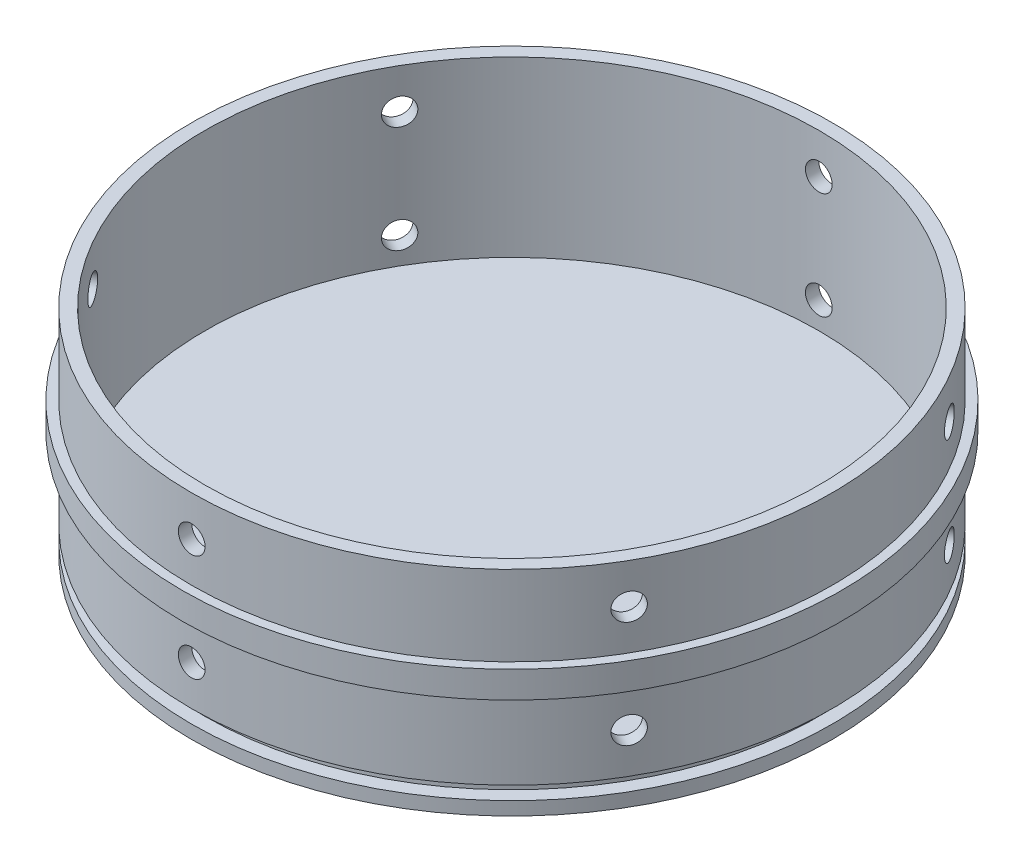
SolidWorks part; units mm, degrees
material "2024-T4"
ref_plane "Front Plane" through (0, 0, 0) normal (0, 0, 1) x (1, 0, 0)
ref_plane "Top Plane" through (0, 0, 0) normal (0, 1, 0) x (1, 0, 0)
ref_plane "Right Plane" through (0, 0, 0) normal (1, 0, 0) x (0, 0, -1)
sketch "Sketch1" plane through (0, 0, 0) normal (0, 1, 0) x (1, 0, 0)
  circle A0 centre (0, 0) radius 78.359
  circle A2 centre (0, 0) radius 76.2
  circle A3 centre (0, 0) radius 73.025
  dimension "D1" = 156.718
  dimension "D2" = 152.4
  dimension "D3" = 3.175
extrude "Boss-Extrude1" add sketch "Sketch1" along normal blind 6.35 contours A0 A2 region at (-78.1374, 0, 0)
extrude "Boss-Extrude2" add sketch "Sketch1<3>" along normal blind 25.4 contours A2 A3 region at (-74.0447, 0, 0)
sketch "Sketch1<3>" plane through (0, 0, 0) normal (0, 1, 0) x (1, 0, 0) same geometry as "Sketch1"
sketch "Sketch2" plane through (0, 0, 0) normal (0, -1, 0) x (1, 0, 0)
  circle A0 centre (0, 0) radius 73.025 construction
  circle A1 centre (0, 0) radius 73.025
  circle A2 centre (0, 0) radius 76.2
  dimension "D1" = 3.175
extrude "Boss-Extrude3" add sketch "Sketch2" along normal blind 25.4
sketch "Sketch3" plane through (0, -25.4, 0) normal (0, -1, 0) x (1, 0, 0)
  circle A1 centre (0, 0) radius 76.2
  circle A2 centre (0, 0) radius 76.2
  dimension "D1" = 0
extrude "Boss-Extrude4" add sketch "Sketch3" against normal blind 9.525
sketch "Sketch5" plane through (0, 0, 0) normal (0, 0, 1) x (1, 0, 0)
  line L0 (-76.2, -25.4) -> (76.2, -25.4) construction
  line L1 (-76.2, 0) -> (-76.2, -25.4) construction
  line L2 (-76.2, -25.4) -> (76.2, -25.4)
  line L3 (-76.2, 0) -> (-76.2, -25.4)
  line L4 (-76.2, -22.225) -> (-73.025, -22.225)
  line L5 (-73.025, -22.225) -> (-73.025, -19.05)
  line L6 (-73.025, -19.05) -> (-76.2, -19.05)
  line L7 (0, 0) -> (0, -25.4) construction
  dimension "D1" = 3.175
  dimension "D2" = 3.175
  dimension "D3" = 3.175
revolve "Cut-Revolve1" cut sketch "Sketch5" angle 360 about L7 region at (-74.6125, -20.6375, 0)
ref_plane "Plane1" through (0, 0, 76.2) normal (0, 0, 1) x (1, 0, 0)
sketch "Sketch6" plane through (0, 0, 76.2) normal (0, 0, 1) x (1, 0, 0)
  line L0 (78.359, 6.35) -> (-78.359, 6.35) construction
  line L1 (78.359, 6.35) -> (-78.359, 6.35)
  line L2 (-76.2, 0) -> (76.2, 0) construction
  line L3 (-76.2, 0) -> (76.2, 0)
  circle A0 centre (0, 15.875) radius 3.175
  circle A1 centre (0, -9.525) radius 3.175
  dimension "D3" = 6.35
  dimension "D4" = 6.35
  dimension "D1" = 9.525
  dimension "D2" = 9.525
extrude "Cut-Extrude1" cut sketch "Sketch6" against normal blind 12.7 contours A0 | A1 region at (0, 15.875, 76.2) region at (0, -9.525, 76.2)
pattern_circular "CirPattern1" count 6 over 360 about axis through (0, 25.4, 0) along (0, -1, 0) of "Cut-Extrude1"
sketch "Sketch7" plane through (0, -15.875, 0) normal (0, 1, 0) x (1, 0, 0)
  circle A0 centre (0, 0) radius 9.525
  circle A1 centre (0, 0) radius 13.335
  dimension "D1" = 19.05
  dimension "D2" = 26.67
